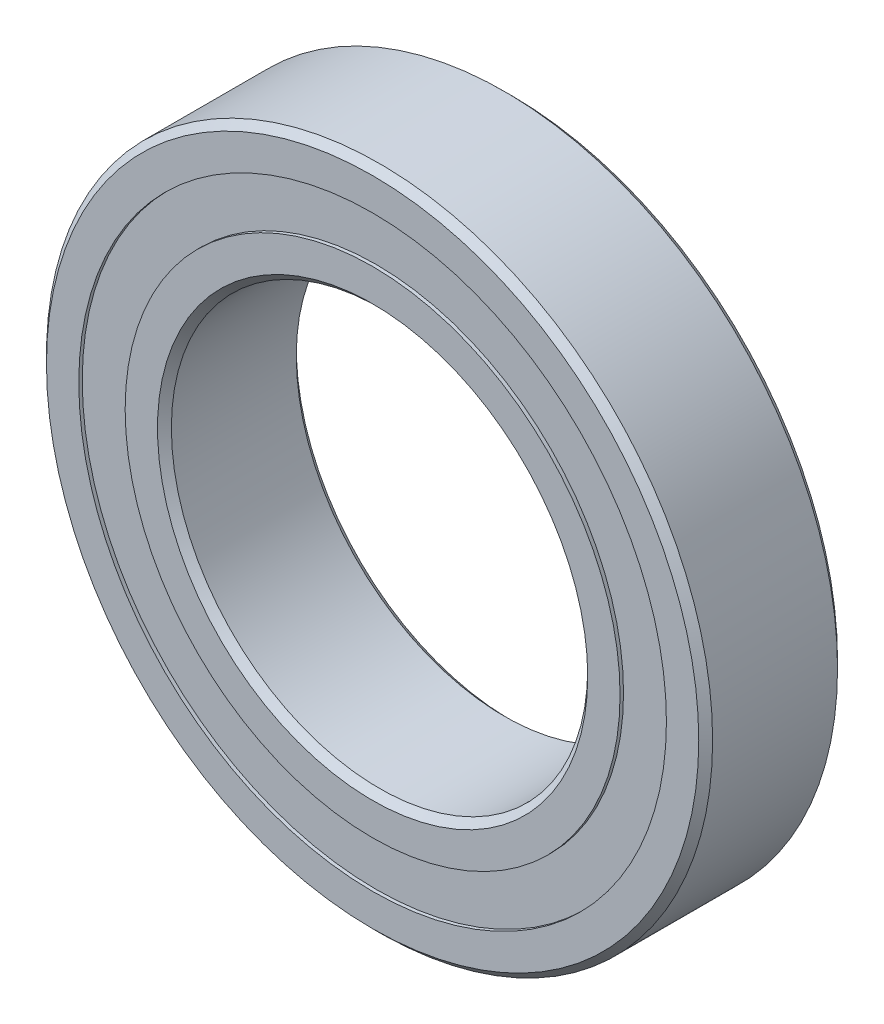
SolidWorks part; units mm, degrees
ref_plane "Front Plane" through (0, 0, 0) normal (0, 0, 1) x (1, 0, 0)
ref_plane "Top Plane" through (0, 0, 0) normal (0, 1, 0) x (1, 0, 0)
ref_plane "Right Plane" through (0, 0, 0) normal (1, 0, 0) x (0, 0, -1)
sketch "Sketch1" plane through (0, 0, 0) normal (1, 0, 0) x (0, 0, -1)
  line L0 (-2.5, 0) -> (2.5, 0) construction
  line L1 (0, 12) -> (0, -12) construction
  line L2 (2.25, 12) -> (-2.25, 12)
  line L3 (-2.25, 12) -> (-2.5, 11.75)
  line L4 (-2.5, 11.75) -> (-2.5, 10.5852)
  line L5 (-2.5, 10.5852) -> (-1.1111, 10.5852)
  line L6 (2.5, 10.5852) -> (1.1111, 10.5852)
  line L7 (2.5, 11.75) -> (2.5, 10.5852)
  line L8 (2.25, 12) -> (2.5, 11.75)
  line L9 (0, 12) -> (0, 9.75) construction
  line L10 (0, 9.75) -> (0, 7.5) construction
  arc A0 (-1.1111, 10.5852) -> (1.1111, 10.5852) centre (0, 9.75) cw
  point P14 (0, 7.5)
  dimension "Width" = 5
  dimension "OD" = 24
  dimension "D1" = 45
  dimension "D2" = 0.25
  dimension "Shaft Dia" = 15
  dimension "D3" = 2.2222
  dimension "D4" = 0.8352
revolve "Revolve1" add sketch "Sketch1" angle 360 about L0
sketch "Sketch3" plane through (0, 0, 0) normal (1, 0, 0) x (0, 0, -1)
  line L0 (-2.5, 8.9148) -> (-1.1111, 8.9148)
  line L1 (0, 12) -> (0, -12) construction
  line L2 (-2.5, 11.75) -> (-2.5, 10.5852) construction
  line L3 (-2.5, 8.9148) -> (-2.5, 7.75)
  line L4 (-2.25, 12) -> (-2.5, 11.75) construction
  line L5 (-2.5, 7.75) -> (-2.25, 7.5)
  line L6 (-2.25, 7.5) -> (2.25, 7.5)
  line L7 (2.25, 12) -> (2.25, -12) construction
  line L8 (2.25, 7.5) -> (2.5, 7.75)
  line L9 (2.5, -11.75) -> (2.5, 11.75) construction
  line L10 (2.5, 7.75) -> (2.5, 8.9148)
  line L11 (2.5, 8.9148) -> (1.1111, 8.9148)
  line L13 (2.25, 12) -> (2.5, 11.75) construction
  arc A0 (1.1111, 10.5852) -> (-1.1111, 10.5852) centre (0, 9.75) ccw construction
  arc A1 (1.1111, 8.9148) -> (-1.1111, 8.9148) centre (0, 9.75) cw
revolve "Revolve3" add sketch "Sketch3" angle 360 about L0
sketch "Sketch4" plane through (0, 0, 0) normal (1, 0, 0) x (0, 0, -1)
  line L0 (-1.39, 9.75) -> (1.39, 9.75)
  arc A2 (-1.39, 9.75) -> (1.39, 9.75) centre (0, 9.75) cw
  arc A3 (1.1111, 10.5852) -> (-1.1111, 10.5852) centre (0, 9.75) ccw construction
revolve "Revolve4" add sketch "Sketch4" angle 360 about L0
ref_axis "Axis1" through (0, 0, -2.5) along (0, 0, 1)
pattern_circular "CirPattern1" count 12 every 30 about axis through (0, 0, -2.5) along (0, 0, 1) of bodies 104
sketch "Sketch5" plane through (0, 0, 0) normal (1, 0, 0) x (0, 0, -1)
  line L0 (-2.5, 10.5852) -> (-1.1111, 10.5852) construction
  line L1 (-2.375, 10.5852) -> (-1.39, 10.5852)
  line L2 (-2.375, 10.5852) -> (-2.375, 8.9148)
  line L3 (-2.375, 8.9148) -> (-1.39, 8.9148)
  line L4 (-1.39, 10.5852) -> (-1.39, 8.9148)
  line L5 (-2.5, 8.9148) -> (-1.1111, 8.9148) construction
  line L6 (2.5, 10.5852) -> (1.1111, 10.5852) construction
  line L7 (2.375, 10.5852) -> (1.39, 10.5852)
  line L8 (2.375, 10.5852) -> (2.375, 8.9148)
  line L9 (2.375, 8.9148) -> (1.39, 8.9148)
  line L10 (1.39, 10.5852) -> (1.39, 8.9148)
  line L11 (2.5, 8.9148) -> (1.1111, 8.9148) construction
  line L12 (-2.25, 12) -> (-2.5, 11.75) construction
  point P18 (-2.375, 11.875)
revolve "Revolve5" add sketch "Sketch5" angle 360 about L0
equation "\"D2@Sketch1\" = \"Width@Sketch1\"*.05"
equation "\"D3@Sketch1\" = \"Width@Sketch1\"/2.25"
equation "\"D4@Sketch1\" = (((\"OD@Sketch1\"-\"Width@Sketch1\")/2)/3.25)/3.5"
equation "\"D2@CirPattern1\" = 360/\"Balls@CirPattern1\""
